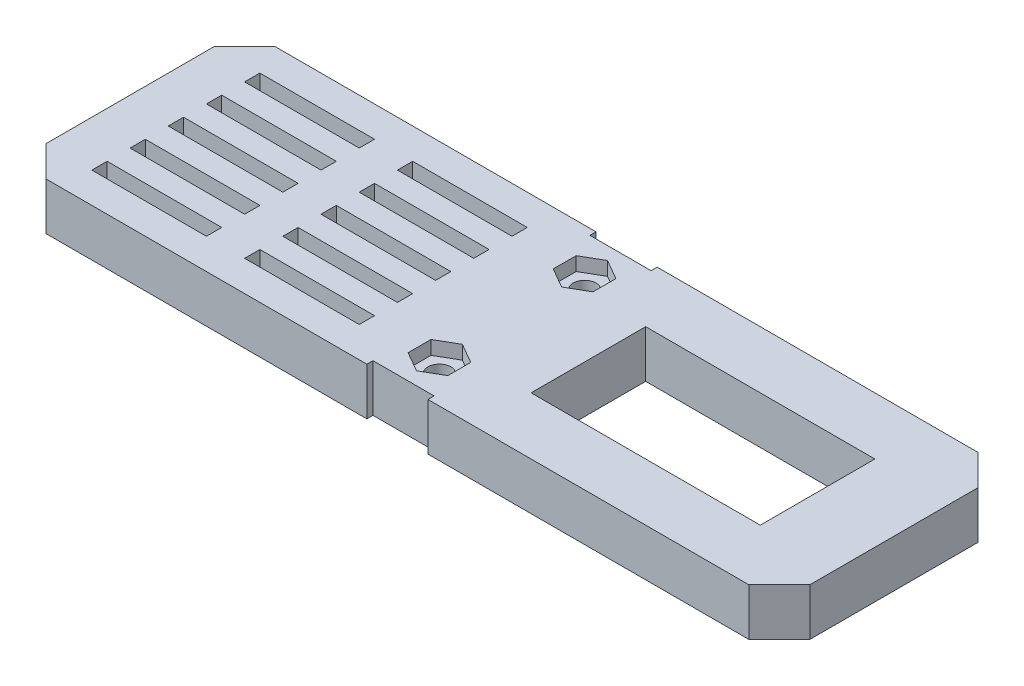
SolidWorks part; units mm, degrees
ref_plane "정면" through (0, 0, 0) normal (0, 0, 1) x (1, 0, 0)
ref_plane "윗면" through (0, 0, 0) normal (0, 1, 0) x (1, 0, 0)
ref_plane "우측면" through (0, 0, 0) normal (1, 0, 0) x (0, 0, -1)
sketch "스케치1" plane through (0, 0, 0) normal (0, 1, 0) x (1, 0, 0)
  line L0 (0, -9.5) -> (0, 9.5) construction
  line L1 (-50, 0) -> (50, 0) construction
  line L2 (-50, -15) -> (50, -15)
  line L3 (-50, -15) -> (-50, 15)
  line L4 (-50, 15) -> (50, 15)
  line L5 (50, -15) -> (50, 15)
  line L6 (-50, -15) -> (50, 15) construction
  line L7 (-50, 15) -> (50, -15) construction
  line L8 (0, 6.4978) -> (2.6, 7.9989)
  line L9 (2.6, 7.9989) -> (2.6, 11.0011)
  line L10 (2.6, 11.0011) -> (0, 12.5022)
  line L11 (0, 12.5022) -> (-2.6, 11.0011)
  line L12 (-2.6, 11.0011) -> (-2.6, 7.9989)
  line L13 (-2.6, 7.9989) -> (0, 6.4978)
  line L14 (2.6, -7.9989) -> (0, -6.4978)
  line L15 (0, -6.4978) -> (-2.6, -7.9989)
  line L16 (-2.6, -7.9989) -> (-2.6, -11.0011)
  line L17 (-2.6, -11.0011) -> (0, -12.5022)
  line L18 (0, -12.5022) -> (2.6, -11.0011)
  line L19 (2.6, -11.0011) -> (2.6, -7.9989)
  line L20 (-24, 9) -> (-9, 9)
  line L21 (10, -7.5) -> (40, -7.5)
  line L22 (10, -7.5) -> (10, 7.5)
  line L23 (10, 7.5) -> (40, 7.5)
  line L24 (40, -7.5) -> (40, 7.5)
  line L25 (10, -7.5) -> (40, 7.5) construction
  line L26 (10, 7.5) -> (40, -7.5) construction
  line L27 (-44, 11) -> (-29, 11)
  line L28 (-44, 11) -> (-44, 9)
  line L29 (-44, 9) -> (-29, 9)
  line L30 (-29, 11) -> (-29, 9)
  line L31 (-24, 11) -> (-9, 11)
  line L32 (-24, 11) -> (-24, 9)
  line L33 (-9, 11) -> (-9, 9)
  line L34 (-44, 4) -> (-29, 4)
  line L35 (-44, 6) -> (-29, 6)
  line L36 (-44, 6) -> (-44, 4)
  line L37 (-29, 6) -> (-29, 4)
  line L38 (-24, 6) -> (-9, 6)
  line L39 (-24, 6) -> (-24, 4)
  line L40 (-24, 4) -> (-9, 4)
  line L41 (-9, 6) -> (-9, 4)
  line L42 (-44, -1) -> (-29, -1)
  line L43 (-44, 1) -> (-29, 1)
  line L44 (-44, 1) -> (-44, -1)
  line L45 (-29, 1) -> (-29, -1)
  line L46 (-24, 1) -> (-9, 1)
  line L47 (-24, 1) -> (-24, -1)
  line L48 (-24, -1) -> (-9, -1)
  line L49 (-9, 1) -> (-9, -1)
  line L50 (-44, -6) -> (-29, -6)
  line L51 (-44, -4) -> (-29, -4)
  line L52 (-44, -4) -> (-44, -6)
  line L53 (-29, -4) -> (-29, -6)
  line L54 (-24, -4) -> (-9, -4)
  line L55 (-24, -4) -> (-24, -6)
  line L56 (-24, -6) -> (-9, -6)
  line L57 (-9, -4) -> (-9, -6)
  line L58 (-44, -11) -> (-29, -11)
  line L59 (-44, -9) -> (-29, -9)
  line L60 (-44, -9) -> (-44, -11)
  line L61 (-29, -9) -> (-29, -11)
  line L62 (-24, -9) -> (-9, -9)
  line L63 (-24, -9) -> (-24, -11)
  line L64 (-24, -11) -> (-9, -11)
  line L65 (-9, -9) -> (-9, -11)
  circle A0 centre (0, 9.5) radius 2.6 construction
  circle A1 centre (0, -9.5) radius 2.6 construction
  circle A2 centre (0, 9.5) radius 1.5
  circle A3 centre (0, -9.5) radius 1.5
  point P4 (0, 0)
  point P7 (0, 0)
  point P26 (25, 0)
  dimension "D2" = 5.2
  dimension "D14" = 3
  dimension "D1" = 19
  dimension "D3" = 30
  dimension "D4" = 50
  dimension "D5" = 30
  dimension "D6" = 25
  dimension "D7" = 15
  dimension "D10" = 4
  dimension "D11" = 2
  dimension "D12" = 15
  dimension "D13" = 6
  dimension "D8" = 2
  dimension "D9" = 5
extrude "보스-돌출1" add sketch "스케치1" along normal blind 3.2 contours L2 L5 L4 L3 L24 L21 L22 L23 L19 L18 L17 L16 L15 L14 L13 L12 L11 L10 L9 L8 L27 L30 L29 L28 L31 L33 L20 L32 L35 L37 L34 L36 L38 L41 L40 L39 L43 L45 L42 L44 L46 L49 | L18 L19 L14 L15 L16 L17 | L12 L13 L8 L9 L10 L11 region at (-1.4978, 0, 0) region at (-1.2603, 0, -7.3171) region at (2.5206, 0, 9.5)
extrude "컷-돌출1" cut sketch "스케치1<3>" against normal blind 1.8 from surface contours L9 L10 L11 L12 L13 L8 | L19 L14 L15 L16 L17 L18 starting at face at (25, 3.2, 0)
sketch "스케치1<3>" plane through (0, 0, 0) normal (0, 1, 0) x (1, 0, 0) same geometry as "스케치1"
chamfer "모따기1" distance 4 angle 45 4 edges at (50, 1.6, -15) (50, 1.6, 15) (-50, 1.6, 15) (-50, 1.6, -15)
sketch "스케치2" plane through (0, 3.2, 0) normal (0, 1, 0) x (1, 0, 0)
  line L0 (-50, 0) -> (50, 0) construction
  line L1 (-50, -11) -> (-50, 11) construction
  line L2 (50, -11) -> (50, 11) construction
  line L3 (-46, 15) -> (46, 15) construction
  line L4 (-4, 15) -> (4, 15)
  line L5 (-4, 15) -> (-4, 14.2)
  line L6 (-4, 14.2) -> (4, 14.2)
  line L7 (4, 15) -> (4, 14.2)
  line L8 (-4, -15) -> (-4, -14.2)
  line L9 (-4, -15) -> (4, -15)
  line L10 (4, -15) -> (4, -14.2)
  line L11 (-4, -14.2) -> (4, -14.2)
  line L12 (0, -14.2) -> (0, 14.2) construction
  point P19 (0, 0)
  dimension "D1" = 8
  dimension "D2" = 0.8
extrude "컷-돌출2" cut sketch "스케치2" against normal through all
sketch "스케치3" plane through (0, 0, 0) normal (0, -1, 0) x (1, 0, 0)
  line L0 (10, 7.5) -> (40, 7.5) construction
  line L1 (10, -7.5) -> (40, -7.5) construction
  line L2 (40, 7.5) -> (40, -7.5) construction
  line L3 (-44, 9) -> (-29, 9) construction
  line L4 (40, -7.5) -> (40, 7.5)
  line L5 (10, -7.5) -> (40, -7.5)
  line L6 (10, 7.5) -> (10, -7.5)
  line L7 (40, 7.5) -> (10, 7.5)
  line L8 (40, -7.5) -> (40, 7.5)
  line L9 (10, -7.5) -> (40, -7.5)
  line L10 (10, 7.5) -> (10, -7.5)
  line L11 (40, 7.5) -> (10, 7.5)
  line L12 (-44, 9) -> (-29, 9)
  line L13 (-44, 11) -> (-44, 9)
  line L14 (-29, 11) -> (-44, 11)
  line L15 (-29, 9) -> (-29, 11)
  line L16 (4, 14.2) -> (-4, 14.2)
  line L17 (-4, 14.2) -> (-4, 15)
  line L18 (-4, 15) -> (-46, 15)
  line L19 (-46, 15) -> (-50, 11)
  line L20 (-50, 11) -> (-50, -11)
  line L21 (-50, -11) -> (-46, -15)
  line L22 (-46, -15) -> (-4, -15)
  line L23 (-4, -15) -> (-4, -14.2)
  line L24 (-4, -14.2) -> (4, -14.2)
  line L25 (4, -14.2) -> (4, -15)
  line L26 (4, -15) -> (46, -15)
  line L27 (46, -15) -> (50, -11)
  line L28 (50, -11) -> (50, 11)
  line L29 (50, 11) -> (46, 15)
  line L30 (46, 15) -> (4, 15)
  line L31 (4, 15) -> (4, 14.2)
  line L32 (4, 14.2) -> (-4, 14.2)
  line L33 (-4, 14.2) -> (-4, 15)
  line L34 (-4, 15) -> (-46, 15)
  line L35 (-46, 15) -> (-50, 11)
  line L36 (-50, 11) -> (-50, -11)
  line L37 (-50, -11) -> (-46, -15)
  line L38 (-46, -15) -> (-4, -15)
  line L39 (-4, -15) -> (-4, -14.2)
  line L40 (-4, -14.2) -> (4, -14.2)
  line L41 (4, -14.2) -> (4, -15)
  line L42 (4, -15) -> (46, -15)
  line L43 (46, -15) -> (50, -11)
  line L44 (50, -11) -> (50, 11)
  line L45 (50, 11) -> (46, 15)
  line L46 (46, 15) -> (4, 15)
  line L47 (4, 15) -> (4, 14.2)
  line L48 (-44, 9) -> (-29, 9)
  line L49 (-44, 11) -> (-44, 9)
  line L50 (-29, 11) -> (-44, 11)
  line L51 (-29, 9) -> (-29, 11)
  line L52 (-44, 4) -> (-29, 4)
  line L53 (-44, 6) -> (-44, 4)
  line L54 (-29, 6) -> (-44, 6)
  line L55 (-29, 4) -> (-29, 6)
  line L56 (-44, 4) -> (-29, 4)
  line L57 (-44, 6) -> (-44, 4)
  line L58 (-29, 6) -> (-44, 6)
  line L59 (-29, 4) -> (-29, 6)
  line L60 (-44, -1) -> (-29, -1)
  line L61 (-44, 1) -> (-44, -1)
  line L62 (-29, 1) -> (-44, 1)
  line L63 (-29, -1) -> (-29, 1)
  line L64 (-44, -1) -> (-29, -1)
  line L65 (-44, 1) -> (-44, -1)
  line L66 (-29, 1) -> (-44, 1)
  line L67 (-29, -1) -> (-29, 1)
  line L68 (-44, -6) -> (-29, -6)
  line L69 (-44, -4) -> (-44, -6)
  line L70 (-29, -4) -> (-44, -4)
  line L71 (-29, -6) -> (-29, -4)
  line L72 (-44, -6) -> (-29, -6)
  line L73 (-44, -4) -> (-44, -6)
  line L74 (-29, -4) -> (-44, -4)
  line L75 (-29, -6) -> (-29, -4)
  line L76 (-44, -11) -> (-29, -11)
  line L77 (-44, -9) -> (-44, -11)
  line L78 (-29, -9) -> (-44, -9)
  line L79 (-29, -11) -> (-29, -9)
  line L80 (-44, -11) -> (-29, -11)
  line L81 (-44, -9) -> (-44, -11)
  line L82 (-29, -9) -> (-44, -9)
  line L83 (-29, -11) -> (-29, -9)
  line L84 (-24, -11) -> (-9, -11)
  line L85 (-24, -9) -> (-24, -11)
  line L86 (-9, -9) -> (-24, -9)
  line L87 (-9, -11) -> (-9, -9)
  line L88 (-24, -11) -> (-9, -11)
  line L89 (-24, -9) -> (-24, -11)
  line L90 (-9, -9) -> (-24, -9)
  line L91 (-9, -11) -> (-9, -9)
  line L92 (-24, -6) -> (-9, -6)
  line L93 (-24, -4) -> (-24, -6)
  line L94 (-9, -4) -> (-24, -4)
  line L95 (-9, -6) -> (-9, -4)
  line L96 (-24, -6) -> (-9, -6)
  line L97 (-24, -4) -> (-24, -6)
  line L98 (-9, -4) -> (-24, -4)
  line L99 (-9, -6) -> (-9, -4)
  line L100 (-24, -1) -> (-9, -1)
  line L101 (-24, 1) -> (-24, -1)
  line L102 (-9, 1) -> (-24, 1)
  line L103 (-9, -1) -> (-9, 1)
  line L104 (-24, -1) -> (-9, -1)
  line L105 (-24, 1) -> (-24, -1)
  line L106 (-9, 1) -> (-24, 1)
  line L107 (-9, -1) -> (-9, 1)
  line L108 (-24, 4) -> (-9, 4)
  line L109 (-24, 6) -> (-24, 4)
  line L110 (-9, 6) -> (-24, 6)
  line L111 (-9, 4) -> (-9, 6)
  line L112 (-24, 4) -> (-9, 4)
  line L113 (-24, 6) -> (-24, 4)
  line L114 (-9, 6) -> (-24, 6)
  line L115 (-9, 4) -> (-9, 6)
  line L116 (-24, 9) -> (-9, 9)
  line L117 (-24, 11) -> (-24, 9)
  line L118 (-9, 11) -> (-24, 11)
  line L119 (-9, 9) -> (-9, 11)
  line L120 (-24, 9) -> (-9, 9)
  line L121 (-24, 11) -> (-24, 9)
  line L122 (-9, 11) -> (-24, 11)
  line L123 (-9, 9) -> (-9, 11)
  line L124 (-29, 9) -> (-29, 11) construction
  line L125 (-44, 9) -> (-44, 11) construction
  line L126 (-44, 4) -> (-44, 6) construction
  line L127 (-29, 4) -> (-29, 6) construction
  line L128 (10, 7.5) -> (40, 7.5)
  line L129 (10, -7.5) -> (40, -7.5)
  line L130 (40, 7.5) -> (40, -7.5)
  line L131 (-44, 9) -> (-29, 9)
  line L132 (-29, 9) -> (-29, 11)
  line L133 (-44, 9) -> (-44, 11)
  line L134 (-44, 4) -> (-44, 6)
  line L135 (-29, 4) -> (-29, 6)
  circle A0 centre (0, 9.5) radius 1.5 construction
  circle A1 centre (0, -9.5) radius 1.5 construction
  circle A2 centre (0, 9.5) radius 1.5
  circle A3 centre (0, -9.5) radius 1.5
  circle A4 centre (0, 9.5) radius 2.75
  circle A5 centre (0, -9.5) radius 2.75
  dimension "D13" = 5.5
  dimension "D1" = 0
  dimension "D2" = 0
  dimension "D3" = 0
  dimension "D4" = 0
  dimension "D5" = 0
  dimension "D6" = 0
  dimension "D7" = 0
  dimension "D8" = 0
  dimension "D9" = 0
  dimension "D10" = 0
  dimension "D11" = 0
  dimension "D12" = 0
extrude "보스-돌출2" add sketch "스케치3" along normal blind 3 contours L46 L47 L32 L33 L34 L35 L36 L37 L38 L39 L40 L41 L42 L43 L44 L45 A5 A4 L123 L120 L121 L122 L115 L112 L113 L114 L107 L104 L105 L106 L99 L96 L97 L98 L91 L88 L89 L90 L83 L80 L81 L82 region at (-1.5294, 0, 0)
